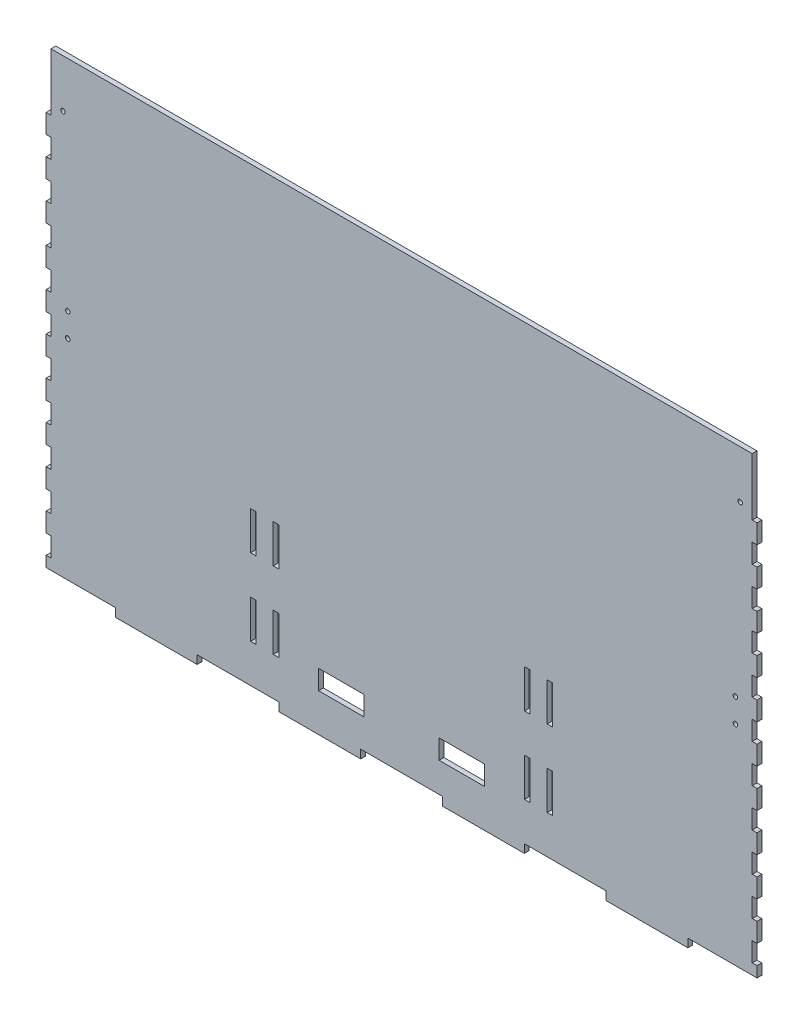
SolidWorks part; units mm, degrees
ref_plane "Front Plane" through (0, 0, 0) normal (0, 0, 1) x (1, 0, 0)
ref_plane "Top Plane" through (0, 0, 0) normal (0, 1, 0) x (1, 0, 0)
ref_plane "Right Plane" through (0, 0, 0) normal (1, 0, 0) x (0, 0, -1)
sketch "Sketch1" plane through (0, 0, 0) normal (0, 0, 1) x (1, 0, 0)
  line L0 (0, 139.7) -> (0, -139.7) construction
  line L1 (-406.4, 139.7) -> (406.4, 139.7)
  line L2 (-406.4, 139.7) -> (-406.4, -139.7)
  line L3 (-406.4, -139.7) -> (406.4, -139.7)
  line L4 (406.4, 139.7) -> (406.4, -139.7)
  line L49 (-381, 127) -> (-381, 114.3)
  line L54 (-381, 139.7) -> (-377.825, 139.7)
  line L55 (-381, 139.7) -> (-381, 127)
  line L56 (-381, 127) -> (-377.825, 127)
  line L57 (-377.825, 139.7) -> (-377.825, 127)
  line L58 (-381, 127) -> (-377.825, 127)
  line L59 (-377.825, 127) -> (-377.825, 114.3)
  line L60 (-381, 114.3) -> (-377.825, 114.3)
  line L61 (-381, 114.3) -> (-381, 101.6)
  line L62 (-381, 114.3) -> (-377.825, 114.3)
  line L63 (-377.825, 114.3) -> (-377.825, 101.6)
  line L64 (-381, 101.6) -> (-377.825, 101.6)
  line L65 (-381, 101.6) -> (-381, 88.9)
  line L66 (-381, 101.6) -> (-377.825, 101.6)
  line L67 (-377.825, 101.6) -> (-377.825, 88.9)
  line L68 (-381, 88.9) -> (-377.825, 88.9)
  line L69 (-381, 88.9) -> (-381, 76.2)
  line L70 (-381, 88.9) -> (-377.825, 88.9)
  line L71 (-377.825, 88.9) -> (-377.825, 76.2)
  line L72 (-381, 76.2) -> (-377.825, 76.2)
  line L73 (-381, 76.2) -> (-381, 63.5)
  line L74 (-381, 76.2) -> (-377.825, 76.2)
  line L75 (-377.825, 76.2) -> (-377.825, 63.5)
  line L76 (-381, 63.5) -> (-377.825, 63.5)
  line L77 (-381, 63.5) -> (-381, 50.8)
  line L78 (-381, 63.5) -> (-377.825, 63.5)
  line L79 (-377.825, 63.5) -> (-377.825, 50.8)
  line L80 (-381, 50.8) -> (-377.825, 50.8)
  line L81 (-381, 50.8) -> (-381, 38.1)
  line L82 (-381, 50.8) -> (-377.825, 50.8)
  line L83 (-377.825, 50.8) -> (-377.825, 38.1)
  line L84 (-381, 38.1) -> (-377.825, 38.1)
  line L85 (-381, 38.1) -> (-381, 25.4)
  line L86 (-381, 38.1) -> (-377.825, 38.1)
  line L87 (-377.825, 38.1) -> (-377.825, 25.4)
  line L88 (-381, 25.4) -> (-377.825, 25.4)
  line L89 (377.825, 127) -> (377.825, 114.3)
  line L90 (377.825, 139.7) -> (381, 139.7)
  line L91 (377.825, 139.7) -> (377.825, 127)
  line L92 (377.825, 127) -> (381, 127)
  line L93 (381, 139.7) -> (381, 127)
  line L94 (377.825, 127) -> (381, 127)
  line L95 (381, 127) -> (381, 114.3)
  line L96 (377.825, 114.3) -> (381, 114.3)
  line L97 (377.825, 114.3) -> (377.825, 101.6)
  line L98 (377.825, 114.3) -> (381, 114.3)
  line L99 (381, 114.3) -> (381, 101.6)
  line L100 (377.825, 101.6) -> (381, 101.6)
  line L101 (377.825, 101.6) -> (377.825, 88.9)
  line L102 (377.825, 101.6) -> (381, 101.6)
  line L103 (381, 101.6) -> (381, 88.9)
  line L104 (377.825, 88.9) -> (381, 88.9)
  line L105 (377.825, 88.9) -> (377.825, 76.2)
  line L106 (377.825, 88.9) -> (381, 88.9)
  line L107 (381, 88.9) -> (381, 76.2)
  line L108 (377.825, 76.2) -> (381, 76.2)
  line L109 (377.825, 76.2) -> (377.825, 63.5)
  line L110 (377.825, 76.2) -> (381, 76.2)
  line L111 (381, 76.2) -> (381, 63.5)
  line L112 (377.825, 63.5) -> (381, 63.5)
  line L113 (377.825, 63.5) -> (377.825, 50.8)
  line L114 (377.825, 63.5) -> (381, 63.5)
  line L115 (381, 63.5) -> (381, 50.8)
  line L116 (377.825, 50.8) -> (381, 50.8)
  line L117 (377.825, 50.8) -> (377.825, 38.1)
  line L118 (377.825, 50.8) -> (381, 50.8)
  line L119 (381, 50.8) -> (381, 38.1)
  line L120 (377.825, 38.1) -> (381, 38.1)
  line L121 (377.825, 38.1) -> (377.825, 25.4)
  line L122 (377.825, 38.1) -> (381, 38.1)
  line L123 (381, 38.1) -> (381, 25.4)
  line L124 (377.825, 25.4) -> (381, 25.4)
  line L125 (-352.2133, -134.112) -> (-352.2133, -139.7)
  line L126 (-406.4, -134.112) -> (-352.2133, -134.112)
  line L127 (-406.4, -134.112) -> (-406.4, -139.7)
  line L128 (-406.4, -139.7) -> (-352.2133, -139.7)
  line L129 (-352.2133, -134.112) -> (-352.2133, -139.7)
  line L130 (-352.2133, -134.112) -> (-298.0267, -134.112)
  line L131 (-298.0267, -134.112) -> (-298.0267, -139.7)
  line L132 (-352.2133, -139.7) -> (-298.0267, -139.7)
  line L133 (-298.0267, -134.112) -> (-298.0267, -139.7)
  line L134 (-298.0267, -134.112) -> (-243.84, -134.112)
  line L135 (-243.84, -134.112) -> (-243.84, -139.7)
  line L136 (-298.0267, -139.7) -> (-243.84, -139.7)
  line L137 (-243.84, -134.112) -> (-243.84, -139.7)
  line L138 (-243.84, -134.112) -> (-189.6533, -134.112)
  line L139 (-189.6533, -134.112) -> (-189.6533, -139.7)
  line L140 (-243.84, -139.7) -> (-189.6533, -139.7)
  line L141 (-189.6533, -134.112) -> (-189.6533, -139.7)
  line L142 (-189.6533, -134.112) -> (-135.4667, -134.112)
  line L143 (-135.4667, -134.112) -> (-135.4667, -139.7)
  line L144 (-189.6533, -139.7) -> (-135.4667, -139.7)
  line L145 (-135.4667, -134.112) -> (-135.4667, -139.7)
  line L146 (-135.4667, -134.112) -> (-81.28, -134.112)
  line L147 (-81.28, -134.112) -> (-81.28, -139.7)
  line L148 (-135.4667, -139.7) -> (-81.28, -139.7)
  line L149 (-81.28, -134.112) -> (-81.28, -139.7)
  line L150 (-81.28, -134.112) -> (-27.0933, -134.112)
  line L151 (-27.0933, -134.112) -> (-27.0933, -139.7)
  line L152 (-81.28, -139.7) -> (-27.0933, -139.7)
  line L153 (-27.0933, -134.112) -> (-27.0933, -139.7)
  line L154 (-27.0933, -134.112) -> (27.0933, -134.112)
  line L155 (27.0933, -134.112) -> (27.0933, -139.7)
  line L156 (-27.0933, -139.7) -> (27.0933, -139.7)
  line L157 (27.0933, -134.112) -> (27.0933, -139.7)
  line L158 (27.0933, -134.112) -> (81.28, -134.112)
  line L159 (81.28, -134.112) -> (81.28, -139.7)
  line L160 (27.0933, -139.7) -> (81.28, -139.7)
  line L161 (81.28, -134.112) -> (81.28, -139.7)
  line L162 (81.28, -134.112) -> (135.4667, -134.112)
  line L163 (135.4667, -134.112) -> (135.4667, -139.7)
  line L164 (81.28, -139.7) -> (135.4667, -139.7)
  line L165 (135.4667, -134.112) -> (135.4667, -139.7)
  line L166 (135.4667, -134.112) -> (189.6533, -134.112)
  line L167 (189.6533, -134.112) -> (189.6533, -139.7)
  line L168 (135.4667, -139.7) -> (189.6533, -139.7)
  line L169 (189.6533, -134.112) -> (189.6533, -139.7)
  line L170 (189.6533, -134.112) -> (243.84, -134.112)
  line L171 (243.84, -134.112) -> (243.84, -139.7)
  line L172 (189.6533, -139.7) -> (243.84, -139.7)
  line L173 (243.84, -134.112) -> (243.84, -139.7)
  line L174 (243.84, -134.112) -> (298.0267, -134.112)
  line L175 (298.0267, -134.112) -> (298.0267, -139.7)
  line L176 (243.84, -139.7) -> (298.0267, -139.7)
  line L177 (298.0267, -134.112) -> (298.0267, -139.7)
  line L178 (298.0267, -134.112) -> (352.2133, -134.112)
  line L179 (352.2133, -134.112) -> (352.2133, -139.7)
  line L180 (298.0267, -139.7) -> (352.2133, -139.7)
  line L181 (352.2133, -134.112) -> (352.2133, -139.7)
  line L182 (352.2133, -134.112) -> (406.4, -134.112)
  line L183 (406.4, -134.112) -> (406.4, -139.7)
  line L184 (352.2133, -139.7) -> (406.4, -139.7)
  line L205 (-90.678, 84.5227) -> (-90.678, -139.7) construction
  line L206 (90.678, 84.5227) -> (90.678, -139.7) construction
  line L207 (-90.678, -27.5886) -> (90.678, -27.5886) construction
  line L208 (-381, 25.4) -> (-381, 12.7)
  line L209 (-381, 25.4) -> (-377.825, 25.4)
  line L210 (-377.825, 25.4) -> (-377.825, 12.7)
  line L211 (-381, 12.7) -> (-377.825, 12.7)
  line L212 (-381, 12.7) -> (-381, 0)
  line L213 (-381, 12.7) -> (-377.825, 12.7)
  line L214 (-377.825, 12.7) -> (-377.825, 0)
  line L215 (-381, 0) -> (-377.825, 0)
  line L224 (-377.825, 0) -> (377.825, 0) construction
  line L229 (377.825, 25.4) -> (377.825, 12.7)
  line L230 (377.825, 25.4) -> (381, 25.4)
  line L231 (381, 25.4) -> (381, 12.7)
  line L232 (377.825, 12.7) -> (381, 12.7)
  line L233 (377.825, 12.7) -> (377.825, 0)
  line L234 (377.825, 12.7) -> (381, 12.7)
  line L235 (381, 12.7) -> (381, 0)
  line L236 (377.825, 0) -> (381, 0)
  line L237 (-381, 0) -> (-381, -12.7)
  line L238 (-381, 0) -> (-377.825, 0)
  line L239 (-377.825, 0) -> (-377.825, -12.7)
  line L240 (-381, -12.7) -> (-377.825, -12.7)
  line L241 (-381, -12.7) -> (-381, -25.4)
  line L242 (-381, -12.7) -> (-377.825, -12.7)
  line L243 (-377.825, -12.7) -> (-377.825, -25.4)
  line L244 (-381, -25.4) -> (-377.825, -25.4)
  line L245 (-381, -25.4) -> (-381, -38.1)
  line L246 (-381, -25.4) -> (-377.825, -25.4)
  line L247 (-377.825, -25.4) -> (-377.825, -38.1)
  line L248 (-381, -38.1) -> (-377.825, -38.1)
  line L249 (-381, -38.1) -> (-381, -50.8)
  line L250 (-381, -38.1) -> (-377.825, -38.1)
  line L251 (-377.825, -38.1) -> (-377.825, -50.8)
  line L252 (-381, -50.8) -> (-377.825, -50.8)
  line L253 (-381, -50.8) -> (-381, -63.5)
  line L254 (-381, -50.8) -> (-377.825, -50.8)
  line L255 (-377.825, -50.8) -> (-377.825, -63.5)
  line L256 (-381, -63.5) -> (-377.825, -63.5)
  line L257 (-381, -63.5) -> (-381, -76.2)
  line L258 (-381, -63.5) -> (-377.825, -63.5)
  line L259 (-377.825, -63.5) -> (-377.825, -76.2)
  line L260 (-381, -76.2) -> (-377.825, -76.2)
  line L261 (-381, -76.2) -> (-381, -88.9)
  line L262 (-381, -76.2) -> (-377.825, -76.2)
  line L263 (-377.825, -76.2) -> (-377.825, -88.9)
  line L264 (-381, -88.9) -> (-377.825, -88.9)
  line L265 (-381, -88.9) -> (-381, -101.6)
  line L266 (-381, -88.9) -> (-377.825, -88.9)
  line L267 (-377.825, -88.9) -> (-377.825, -101.6)
  line L268 (-381, -101.6) -> (-377.825, -101.6)
  line L269 (-381, -101.6) -> (-381, -114.3)
  line L270 (-381, -101.6) -> (-377.825, -101.6)
  line L271 (-377.825, -101.6) -> (-377.825, -114.3)
  line L272 (-381, -114.3) -> (-377.825, -114.3)
  line L273 (-381, -114.3) -> (-381, -127)
  line L274 (-381, -114.3) -> (-377.825, -114.3)
  line L275 (-377.825, -114.3) -> (-377.825, -127)
  line L276 (-381, -127) -> (-377.825, -127)
  line L277 (-381, -127) -> (-381, -139.7)
  line L278 (-381, -127) -> (-377.825, -127)
  line L279 (-377.825, -127) -> (-377.825, -139.7)
  line L280 (-381, -139.7) -> (-377.825, -139.7)
  line L281 (377.825, 0) -> (377.825, -12.7)
  line L282 (377.825, 0) -> (381, 0)
  line L283 (381, 0) -> (381, -12.7)
  line L284 (377.825, -12.7) -> (381, -12.7)
  line L285 (377.825, -12.7) -> (377.825, -25.4)
  line L286 (377.825, -12.7) -> (381, -12.7)
  line L287 (381, -12.7) -> (381, -25.4)
  line L288 (377.825, -25.4) -> (381, -25.4)
  line L289 (377.825, -25.4) -> (377.825, -38.1)
  line L290 (377.825, -25.4) -> (381, -25.4)
  line L291 (381, -25.4) -> (381, -38.1)
  line L292 (377.825, -38.1) -> (381, -38.1)
  line L293 (377.825, -38.1) -> (377.825, -50.8)
  line L294 (377.825, -38.1) -> (381, -38.1)
  line L295 (381, -38.1) -> (381, -50.8)
  line L296 (377.825, -50.8) -> (381, -50.8)
  line L297 (377.825, -50.8) -> (377.825, -63.5)
  line L298 (377.825, -50.8) -> (381, -50.8)
  line L299 (381, -50.8) -> (381, -63.5)
  line L300 (377.825, -63.5) -> (381, -63.5)
  line L301 (377.825, -63.5) -> (377.825, -76.2)
  line L302 (377.825, -63.5) -> (381, -63.5)
  line L303 (381, -63.5) -> (381, -76.2)
  line L304 (377.825, -76.2) -> (381, -76.2)
  line L305 (377.825, -76.2) -> (377.825, -88.9)
  line L306 (377.825, -76.2) -> (381, -76.2)
  line L307 (381, -76.2) -> (381, -88.9)
  line L308 (377.825, -88.9) -> (381, -88.9)
  line L309 (377.825, -88.9) -> (377.825, -101.6)
  line L310 (377.825, -88.9) -> (381, -88.9)
  line L311 (381, -88.9) -> (381, -101.6)
  line L312 (377.825, -101.6) -> (381, -101.6)
  line L313 (377.825, -101.6) -> (377.825, -114.3)
  line L314 (377.825, -101.6) -> (381, -101.6)
  line L315 (381, -101.6) -> (381, -114.3)
  line L316 (377.825, -114.3) -> (381, -114.3)
  line L317 (377.825, -114.3) -> (377.825, -127)
  line L318 (377.825, -114.3) -> (381, -114.3)
  line L319 (381, -114.3) -> (381, -127)
  line L320 (377.825, -127) -> (381, -127)
  line L321 (377.825, -127) -> (377.825, -139.7)
  line L322 (377.825, -127) -> (381, -127)
  line L323 (381, -127) -> (381, -139.7)
  line L324 (377.825, -139.7) -> (381, -139.7)
  point P6 (0, 0)
  point P128 (0, -27.5886)
  point P153 (0, 0)
  dimension "D4" = 12.7
  dimension "D5" = 3.175
  dimension "D10" = 181.356
  dimension "D12" = 755.65
  dimension "D8" = 812.8
  dimension "D11" = 54.1867
  dimension "D2" = 273.812
  dimension "D9" = 279.4
  dimension "D3" = 22
  dimension "D7" = 15
  dimension "D6" = 22
extrude "Main Extrude" add sketch "Sketch1" along normal blind 3.175 contours L321 L317 L313 L309 L305 L301 L297 L293 L289 L285 L281 L233 L229 L121 L117 L113 L109 L105 L101 L97 L89 L91 L1 L57 L59 L63 L67 L71 L75 L79 L83 L87 L210 L214 L239 L243 L247 L251 L255 L259 L263 L267 L271 L275 L279 L126 L130 L134 L138 L142 L146 | L277 L273 L269 L265 L261 L257 L253 L249 L245 L241 L237 L212 L208 L85 L81 L77 L73 L69 L65 L61 L49 L55 L1 L2 L126 | L319 L323 L182 L4 L1 L93 L95 L99 L103 L107 L111 L115 L119 L123 L231 L235 L283 L287 L291 L295 L299 L303 L307 L311 L315 | L126 L279 L3 L125 | L135 L134 L131 L3 | L143 L142 L139 L3 | L151 L150 L147 L3 | L159 L158 L155 L3 | L167 L166 L163 L3 | L175 L174 L171 L3 | L323 L182 L321 L184 | L89 L96 L95 L92 | L101 L104 L103 L100 | L109 L112 L111 L108 | L117 L120 L119 L116 | L229 L232 L231 L124 | L281 L284 L283 L236 | L289 L292 L291 L288 | L297 L300 L299 L296 | L305 L308 L307 L304 | L313 L316 L315 L312 | L323 L320 L321 L182 | L49 L60 L59 L56 | L65 L68 L67 L64 | L73 L76 L75 L72 | L81 L84 L83 L80 | L208 L211 L210 L88 | L237 L240 L239 L215 | L245 L248 L247 L244 | L253 L256 L255 L252 | L261 L264 L263 L260 | L269 L272 L271 L268 | L279 L276 L277 L126 | L277 L126 L2 L3 | L321 L182 L179 L3 | L182 L323 L3 L4 | L279 L126 L277 L128 region at (-393.7, 2.794, 0) region at (-393.7, -136.906, 0) region at (0, 2.794, 0) region at (-379.4125, 120.65, 0) region at (-379.4125, -130.556, 0) region at (-379.4125, -136.906, 0) region at (-365.0192, -136.906, 0) region at (393.7, 2.794, 0) region at (379.4125, 120.65, 0) region at (-379.4125, 95.25, 0) region at (-379.4125, -107.95, 0) region at (-270.9333, -136.906, 0) region at (393.7, -136.906, 0) region at (379.4125, 95.25, 0) region at (-379.4125, 69.85, 0) region at (-379.4125, -82.55, 0) region at (379.4125, -136.906, 0) region at (379.4125, -130.556, 0) region at (-162.56, -136.906, 0) region at (365.0192, -136.906, 0) region at (379.4125, 69.85, 0) region at (-379.4125, 44.45, 0) region at (-379.4125, -57.15, 0) region at (379.4125, -107.95, 0) region at (-54.1867, -136.906, 0) region at (270.9333, -136.906, 0) region at (379.4125, 44.45, 0) region at (-379.4125, 19.05, 0) region at (-379.4125, -31.75, 0) region at (379.4125, -82.55, 0) region at (54.1867, -136.906, 0) region at (162.56, -136.906, 0) region at (379.4125, 19.05, 0) region at (-379.4125, -6.35, 0) region at (379.4125, -57.15, 0) region at (379.4125, -6.35, 0) region at (379.4125, -31.75, 0)
sketch "Sketch8" plane through (0, 0, 3.175) normal (0, 0, 1) x (1, 0, 0)
  line L0 (-406.4, 139.7) -> (-406.4, -139.7) construction
  line L1 (-381, 28.2575) -> (-384.175, 28.2575)
  line L2 (-381, 28.2575) -> (-381, -3.6195)
  line L3 (-381, -3.6195) -> (-384.175, -3.6195)
  line L4 (-384.175, 28.2575) -> (-384.175, -3.6195)
  line L5 (-406.4, -139.7) -> (-352.2133, -139.7) construction
  line L6 (381, 28.2575) -> (384.175, 28.2575)
  line L7 (381, 28.2575) -> (381, -3.6195)
  line L8 (381, -3.6195) -> (384.175, -3.6195)
  line L9 (384.175, 28.2575) -> (384.175, -3.6195)
  line L11 (-381, 88.9) -> (-381, 76.2) construction
  line L12 (-352.2133, -134.112) -> (-298.0267, -134.112) construction
  line L13 (381, 88.9) -> (381, 76.2) construction
  line L14 (-393.7, -120.65) -> (393.7, -120.65) construction
  circle A0 centre (-393.7, -120.65) radius 1.5
  circle A1 centre (393.7, -120.65) radius 1.5
  point P6 (0, -120.65)
  point P16 (-384.175, 12.319)
  dimension "D5" = 3
  dimension "D1" = 31.877
  dimension "D2" = 3.175
  dimension "D3" = 146.431
  dimension "D4" = 19.05
  dimension "D6" = 12.7
extrude "Mount Holes" cut sketch "Sketch8" against normal through all
sketch "Sketch3" plane through (0, 0, 3.175) normal (0, 0, 1) x (1, 0, 0)
  line L0 (-135.4667, -134.112) -> (-81.28, -134.112) construction
  line L1 (-96.52, 126.492) -> (-84.836, 126.492)
  line L2 (-96.52, 126.492) -> (-96.52, -134.112)
  line L3 (-96.52, -134.112) -> (-84.836, -134.112)
  line L4 (-84.836, 126.492) -> (-84.836, -134.112)
  line L5 (81.28, -134.112) -> (135.4667, -134.112) construction
  line L6 (84.836, 126.492) -> (96.52, 126.492)
  line L7 (84.836, 126.492) -> (84.836, -134.112)
  line L8 (84.836, -134.112) -> (96.52, -134.112)
  line L9 (96.52, 126.492) -> (96.52, -134.112)
  line L10 (-84.836, -3.81) -> (84.836, -3.81) construction
  line L12 (-106.553, 10.3505) -> (-74.803, 10.3505)
  line L13 (-106.553, 10.3505) -> (-106.553, 0.8255)
  line L14 (-106.553, 0.8255) -> (-74.803, 0.8255)
  line L15 (-74.803, 10.3505) -> (-74.803, 0.8255)
  line L16 (74.803, 10.3505) -> (106.553, 10.3505)
  line L17 (74.803, 10.3505) -> (74.803, 0.8255)
  line L18 (74.803, 0.8255) -> (106.553, 0.8255)
  line L19 (106.553, 10.3505) -> (106.553, 0.8255)
  line L20 (-96.52, 126.492) -> (-92.6465, 126.492)
  line L21 (-96.52, 126.492) -> (-96.52, 82.042)
  line L22 (-96.52, 82.042) -> (-92.6465, 82.042)
  line L23 (-92.6465, 126.492) -> (-92.6465, 82.042)
  line L24 (-84.836, 126.492) -> (-88.7095, 126.492)
  line L25 (-84.836, 126.492) -> (-84.836, 82.042)
  line L26 (-84.836, 82.042) -> (-88.7095, 82.042)
  line L27 (-88.7095, 126.492) -> (-88.7095, 82.042)
  line L28 (84.836, 126.492) -> (88.7095, 126.492)
  line L29 (84.836, 126.492) -> (84.836, 82.042)
  line L30 (84.836, 82.042) -> (88.7095, 82.042)
  line L31 (88.7095, 126.492) -> (88.7095, 82.042)
  line L32 (96.52, 126.492) -> (92.6465, 126.492)
  line L33 (96.52, 126.492) -> (96.52, 82.042)
  line L34 (96.52, 82.042) -> (92.6465, 82.042)
  line L35 (92.6465, 126.492) -> (92.6465, 82.042)
  point P14 (-90.678, 126.492)
  point P15 (90.678, 126.492)
  point P16 (0, -3.81)
  point P27 (-90.678, 10.3505)
  point P28 (90.678, 10.3505)
  point P29 (-74.803, 5.588)
  dimension "D1" = 11.684
  dimension "D2" = 260.604
  dimension "D3" = 181.356
  dimension "D4" = 9.525
  dimension "D5" = 139.7
  dimension "D6" = 31.75
  dimension "D8" = 3.937
  dimension "D7" = 44.45
extrude "Door Slots" [suppressed] cut sketch "Sketch3" against normal through all contours L2 L12 L4 L1 | L2 L14 L4 L12 | L15 L12 L4 L14 | L13 L14 L2 L12 | L14 L2 L3 L4 | L7 L16 L9 L6 | L7 L18 L9 L16 | L19 L16 L9 L18 | L17 L18 L7 L16 | L18 L7 L8 L9
sketch "Sketch4" plane through (0, 0, 0) normal (0, 0, 1) x (1, 0, 0)
  line L1 (-81.28, -139.7) -> (-27.0933, -139.7) construction
  line L2 (-55.88, -112.41) -> (-52.578, -112.41)
  line L3 (-52.578, -112.41) -> (-52.578, -106.172)
  line L4 (-52.578, -106.172) -> (-1.778, -106.172)
  line L5 (-1.778, -106.172) -> (-1.778, -112.41)
  line L6 (-1.778, -112.41) -> (1.524, -112.41)
  line L9 (-55.88, -112.41) -> (-55.88, -134.112)
  line L10 (-55.88, -134.112) -> (-52.578, -134.112)
  line L11 (-52.578, -134.112) -> (-52.578, -139.7)
  line L12 (1.524, -112.41) -> (1.524, -134.112)
  line L13 (1.524, -134.112) -> (-1.778, -134.112)
  line L14 (-1.778, -134.112) -> (-1.778, -139.7)
  line L15 (-52.578, -139.7) -> (-1.778, -139.7)
  line L16 (-27.0933, -134.112) -> (27.0933, -134.112) construction
  line L17 (-27.0933, -134.112) -> (27.0933, -134.112) construction
  line L18 (12.128, -101.642) -> (42.228, -101.642)
  line L19 (12.128, -101.642) -> (12.128, -114.492)
  line L20 (12.128, -114.492) -> (42.228, -114.492)
  line L21 (42.228, -101.642) -> (42.228, -114.492)
  line L24 (-96.52, -134.112) -> (-84.836, -134.112) construction
  line L25 (84.836, -134.112) -> (96.52, -134.112) construction
  point P9 (-27.178, -106.172)
  point P10 (-27.178, -139.7)
  point P22 (27.178, -114.492)
  point P25 (90.678, -134.112)
  point P26 (12.128, -108.067)
  point P30 (-90.678, -134.112)
  dimension "D1" = 50.8
  dimension "D2" = 3.302
  dimension "D4" = 21.702
  dimension "D5" = 30.1
  dimension "D6" = 12.85
  dimension "D9" = 63.5
  dimension "D8" = 63.5
  dimension "D3" = 27.94
  dimension "D7" = 26.045
extrude "Trough and Lever Holes" [suppressed] cut sketch "Sketch4" along normal through all contours L11 L15 L14 L13 L12 L6 L5 L4 L3 L2 L9 L10 | L21 L18 L19 L20
sketch "Sketch5" plane through (0, 0, 3.175) normal (0, 0, 1) x (1, 0, 0)
  line L0 (-90.678, 126.492) -> (-90.678, -134.112) construction
  line L1 (-96.52, 126.492) -> (-84.836, 126.492) construction
  line L2 (-96.52, -134.112) -> (-84.836, -134.112) construction
  line L3 (90.678, 126.492) -> (90.678, -134.112) construction
  line L4 (84.836, 126.492) -> (96.52, 126.492) construction
  line L5 (84.836, -134.112) -> (96.52, -134.112) construction
  line L6 (-135.4667, -134.112) -> (-81.28, -134.112) construction
  line L19 (-99.998, -134.112) -> (-96.3199, -134.112)
  line L20 (-99.998, -134.112) -> (-99.998, -108.712)
  line L21 (-99.998, -108.712) -> (-96.3199, -108.712)
  line L22 (-96.3199, -134.112) -> (-96.3199, -108.712)
  line L24 (-99.998, -108.712) -> (-96.3199, -108.712)
  line L25 (-99.998, -108.712) -> (-99.998, -83.312)
  line L26 (-99.998, -83.312) -> (-96.3199, -83.312)
  line L27 (-96.3199, -108.712) -> (-96.3199, -83.312)
  line L28 (-96.3199, -83.312) -> (-99.998, -83.312)
  line L29 (-96.3199, -83.312) -> (-96.3199, -57.912)
  line L30 (-96.3199, -57.912) -> (-99.998, -57.912)
  line L31 (-99.998, -83.312) -> (-99.998, -57.912)
  line L32 (-99.998, -57.912) -> (-96.3199, -57.912)
  line L33 (-99.998, -57.912) -> (-99.998, -32.512)
  line L34 (-99.998, -32.512) -> (-96.3199, -32.512)
  line L35 (-96.3199, -57.912) -> (-96.3199, -32.512)
  line L36 (-96.3199, -32.512) -> (-99.998, -32.512)
  line L37 (-96.3199, -32.512) -> (-96.3199, -7.112)
  line L38 (-96.3199, -7.112) -> (-99.998, -7.112)
  line L39 (-99.998, -32.512) -> (-99.998, -7.112)
  line L40 (-81.358, -108.712) -> (-85.0361, -108.712)
  line L41 (-85.0361, -134.112) -> (-85.0361, -108.712)
  line L42 (-81.358, -134.112) -> (-85.0361, -134.112)
  line L43 (-81.358, -134.112) -> (-81.358, -108.712)
  line L44 (-81.358, -83.312) -> (-85.0361, -83.312)
  line L45 (-85.0361, -108.712) -> (-85.0361, -83.312)
  line L46 (-81.358, -108.712) -> (-85.0361, -108.712)
  line L47 (-81.358, -108.712) -> (-81.358, -83.312)
  line L48 (-85.0361, -57.912) -> (-81.358, -57.912)
  line L49 (-81.358, -83.312) -> (-81.358, -57.912)
  line L50 (-85.0361, -83.312) -> (-81.358, -83.312)
  line L51 (-85.0361, -83.312) -> (-85.0361, -57.912)
  line L52 (-81.358, -32.512) -> (-85.0361, -32.512)
  line L53 (-85.0361, -57.912) -> (-85.0361, -32.512)
  line L54 (-81.358, -57.912) -> (-85.0361, -57.912)
  line L55 (-81.358, -57.912) -> (-81.358, -32.512)
  line L56 (-85.0361, -7.112) -> (-81.358, -7.112)
  line L57 (-81.358, -32.512) -> (-81.358, -7.112)
  line L58 (-85.0361, -32.512) -> (-81.358, -32.512)
  line L59 (-85.0361, -32.512) -> (-85.0361, -7.112)
  line L60 (0, -1.7463) -> (0, 1.7463) construction
  line L61 (99.998, -108.712) -> (96.3199, -108.712)
  line L62 (96.3199, -134.112) -> (96.3199, -108.712)
  line L63 (99.998, -134.112) -> (96.3199, -134.112)
  line L64 (99.998, -134.112) -> (99.998, -108.712)
  line L65 (99.998, -83.312) -> (96.3199, -83.312)
  line L66 (96.3199, -108.712) -> (96.3199, -83.312)
  line L67 (99.998, -108.712) -> (96.3199, -108.712)
  line L68 (99.998, -108.712) -> (99.998, -83.312)
  line L69 (96.3199, -57.912) -> (99.998, -57.912)
  line L70 (99.998, -83.312) -> (99.998, -57.912)
  line L71 (96.3199, -83.312) -> (99.998, -83.312)
  line L72 (96.3199, -83.312) -> (96.3199, -57.912)
  line L73 (99.998, -32.512) -> (96.3199, -32.512)
  line L74 (96.3199, -57.912) -> (96.3199, -32.512)
  line L75 (99.998, -57.912) -> (96.3199, -57.912)
  line L76 (99.998, -57.912) -> (99.998, -32.512)
  line L77 (96.3199, -7.112) -> (99.998, -7.112)
  line L78 (99.998, -32.512) -> (99.998, -7.112)
  line L79 (96.3199, -32.512) -> (99.998, -32.512)
  line L80 (96.3199, -32.512) -> (96.3199, -7.112)
  line L81 (85.0361, -32.512) -> (85.0361, -7.112)
  line L82 (85.0361, -32.512) -> (81.358, -32.512)
  line L83 (81.358, -32.512) -> (81.358, -7.112)
  line L84 (85.0361, -7.112) -> (81.358, -7.112)
  line L85 (81.358, -57.912) -> (81.358, -32.512)
  line L86 (81.358, -57.912) -> (85.0361, -57.912)
  line L87 (85.0361, -57.912) -> (85.0361, -32.512)
  line L88 (81.358, -32.512) -> (85.0361, -32.512)
  line L89 (85.0361, -83.312) -> (85.0361, -57.912)
  line L90 (85.0361, -83.312) -> (81.358, -83.312)
  line L91 (81.358, -83.312) -> (81.358, -57.912)
  line L92 (85.0361, -57.912) -> (81.358, -57.912)
  line L93 (81.358, -108.712) -> (81.358, -83.312)
  line L94 (81.358, -108.712) -> (85.0361, -108.712)
  line L95 (85.0361, -108.712) -> (85.0361, -83.312)
  line L96 (81.358, -83.312) -> (85.0361, -83.312)
  line L97 (81.358, -134.112) -> (81.358, -108.712)
  line L98 (81.358, -134.112) -> (85.0361, -134.112)
  line L99 (85.0361, -134.112) -> (85.0361, -108.712)
  line L100 (81.358, -108.712) -> (85.0361, -108.712)
  dimension "D1" = 25.4
  dimension "D3" = 5.6419
  dimension "D2" = 9.32
extrude "Door Guide Slots" cut sketch "Sketch5" against normal through all contours L21 L27 L26 L25 | L30 L35 L34 L33 | L48 L55 L52 L53 | L40 L47 L44 L45 | L86 L87 L82 L85 | L94 L95 L90 L93 | L69 L76 L73 L74 | L61 L68 L65 L66 region at (-98.1589, -96.012, 3.175) region at (-98.1589, -45.212, 3.175) region at (-83.1971, -96.012, 3.175) region at (-83.1971, -45.212, 3.175) region at (98.1589, -96.012, 3.175) region at (98.1589, -45.212, 3.175) region at (83.1971, -45.212, 3.175) region at (83.1971, -96.012, 3.175)
sketch "Sketch7" plane through (0, 0, 3.175) normal (0, 0, 1) x (1, 0, 0)
  line L0 (-24.828, -108.067) -> (24.828, -108.067) construction
  line L1 (-54.928, -101.642) -> (-24.828, -101.642)
  line L2 (-54.928, -101.642) -> (-54.928, -114.492)
  line L3 (-54.928, -114.492) -> (-24.828, -114.492)
  line L4 (-24.828, -101.642) -> (-24.828, -114.492)
  line L5 (54.928, -101.642) -> (24.828, -101.642)
  line L6 (54.928, -101.642) -> (54.928, -114.492)
  line L7 (54.928, -114.492) -> (24.828, -114.492)
  line L8 (24.828, -101.642) -> (24.828, -114.492)
  line L9 (0, -108.067) -> (0, 0) construction
  line L10 (-96.52, -134.112) -> (-84.836, -134.112) construction
  line L12 (-135.4667, -134.112) -> (-81.28, -134.112) construction
  point P12 (-54.928, -108.067)
  point P15 (-39.878, -101.642)
  point P18 (-90.678, -134.112)
  dimension "D1" = 12.85
  dimension "D2" = 30.1
  dimension "D3" = 50.8
  dimension "D4" = 26.045
extrude "Lever Holes" cut sketch "Sketch7" against normal through all
sketch "Sketch10" [suppressed] plane through (0, 0, 3.175) normal (0, 0, 1) x (1, 0, 0)
  line L0 (-101.678, 127.492) -> (-79.678, 127.492) construction
  line L2 (-92.6465, 126.492) -> (-88.7095, 126.492) construction
  line L3 (-90.678, 127.492) -> (-90.678, 126.492) construction
  line L4 (79.678, 127.492) -> (101.678, 127.492) construction
  line L5 (90.678, 127.492) -> (90.678, 126.492) construction
  line L6 (88.7095, 126.492) -> (92.6465, 126.492) construction
  circle A0 centre (-101.678, 127.492) radius 1.5
  circle A1 centre (-79.678, 127.492) radius 1.5
  circle A2 centre (79.678, 127.492) radius 1.5
  circle A3 centre (101.678, 127.492) radius 1.5
  dimension "D1" = 3
  dimension "D2" = 22
  dimension "D3" = 1
extrude "Door Guide Mount Holes" [suppressed] cut sketch "Sketch10" against normal through all
sketch "Sketch12" plane through (0, 0, 3.175) normal (0, 0, 1) x (1, 0, 0)
  line L0 (-246.507, 20.193) -> (-246.507, 4.445) construction
  line L1 (-221.107, 20.193) -> (-221.107, 4.445) construction
  line L2 (-246.507, 20.193) -> (-221.107, 20.193) construction
  line L3 (-246.507, 4.445) -> (-221.107, 4.445) construction
  line L4 (-243.332, 133.35) -> (-224.282, 133.35) construction
  line L5 (-406.4, 139.7) -> (406.4, 139.7) construction
  line L6 (-233.807, 20.193) -> (-233.807, 133.35) construction
  line L7 (-243.84, -134.112) -> (-189.6533, -134.112) construction
  line L8 (0, -1.7463) -> (0, 1.7463) construction
  line L9 (233.807, 20.193) -> (233.807, 133.35) construction
  line L10 (243.332, 133.35) -> (224.282, 133.35) construction
  line L11 (246.507, 4.445) -> (221.107, 4.445) construction
  line L12 (246.507, 20.193) -> (221.107, 20.193) construction
  line L13 (221.107, 20.193) -> (221.107, 4.445) construction
  line L14 (246.507, 20.193) -> (246.507, 4.445) construction
  circle A0 centre (-246.507, 20.193) radius 1.5
  circle A1 centre (-246.507, 4.445) radius 1.5
  circle A2 centre (-221.107, 4.445) radius 1.5
  circle A3 centre (-221.107, 20.193) radius 1.5
  circle A4 centre (-243.332, 133.35) radius 1.5
  circle A5 centre (-224.282, 133.35) radius 1.5
  circle A6 centre (224.282, 133.35) radius 1.5
  circle A7 centre (243.332, 133.35) radius 1.5
  circle A8 centre (221.107, 20.193) radius 1.5
  circle A9 centre (221.107, 4.445) radius 1.5
  circle A10 centre (246.507, 4.445) radius 1.5
  circle A11 centre (246.507, 20.193) radius 1.5
  point P12 (-233.807, 133.35)
  dimension "D1" = 3
  dimension "D2" = 233.807
  dimension "D3" = 19.05
  dimension "D4" = 6.35
  dimension "D5" = 25.4
  dimension "D6" = 15.748
  dimension "D7" = 138.557
extrude "Extension Clip Holes" cut sketch "Sketch12" against normal through all
sketch "Sketch11" plane through (0, 0, 3.175) normal (0, 0, 1) x (1, 0, 0)
  line L0 (-232.2195, 139.7) -> (-232.2195, 127)
  line L1 (-232.2195, 127) -> (-235.3945, 127)
  line L2 (-235.3945, 127) -> (-235.3945, 114.3)
  line L3 (-235.3945, 114.3) -> (-232.2195, 114.3)
  line L4 (232.2195, 139.7) -> (232.2195, 127)
  line L5 (232.2195, 127) -> (235.3945, 127)
  line L6 (235.3945, 127) -> (235.3945, 114.3)
  line L7 (235.3945, 114.3) -> (232.2195, 114.3)
  line L9 (-381, 127) -> (-377.825, 127) construction
  line L10 (-377.825, 139.7) -> (-377.825, 127) construction
  line L11 (235.3945, 120.65) -> (-235.3945, 120.65) construction
  line L12 (-232.2195, 114.3) -> (-232.2195, 101.6)
  line L13 (-232.2195, 101.6) -> (-235.3945, 101.6)
  line L14 (-235.3945, 101.6) -> (-235.3945, 88.9)
  line L15 (-235.3945, 88.9) -> (-232.2195, 88.9)
  line L16 (232.2195, 114.3) -> (232.2195, 101.6)
  line L17 (232.2195, 101.6) -> (235.3945, 101.6)
  line L18 (235.3945, 101.6) -> (235.3945, 88.9)
  line L19 (235.3945, 88.9) -> (232.2195, 88.9)
  line L20 (-232.2195, 88.9) -> (-232.2195, 76.2)
  line L21 (-232.2195, 76.2) -> (-235.3945, 76.2)
  line L22 (-235.3945, 76.2) -> (-235.3945, 63.5)
  line L23 (-235.3945, 63.5) -> (-232.2195, 63.5)
  line L24 (232.2195, 88.9) -> (232.2195, 76.2)
  line L25 (232.2195, 76.2) -> (235.3945, 76.2)
  line L26 (235.3945, 76.2) -> (235.3945, 63.5)
  line L27 (235.3945, 63.5) -> (232.2195, 63.5)
  line L28 (-232.2195, 63.5) -> (-232.2195, 50.8)
  line L29 (-232.2195, 50.8) -> (-235.3945, 50.8)
  line L30 (-235.3945, 50.8) -> (-235.3945, 38.1)
  line L31 (-235.3945, 38.1) -> (-232.2195, 38.1)
  line L32 (232.2195, 63.5) -> (232.2195, 50.8)
  line L33 (232.2195, 50.8) -> (235.3945, 50.8)
  line L34 (235.3945, 50.8) -> (235.3945, 38.1)
  line L35 (235.3945, 38.1) -> (232.2195, 38.1)
  line L36 (-232.2195, 38.1) -> (-232.2195, 25.4)
  line L37 (-232.2195, 25.4) -> (-235.3945, 25.4)
  line L38 (-235.3945, 25.4) -> (-235.3945, 12.7)
  line L39 (-235.3945, 12.7) -> (-232.2195, 12.7)
  line L40 (232.2195, 38.1) -> (232.2195, 25.4)
  line L41 (232.2195, 25.4) -> (235.3945, 25.4)
  line L42 (235.3945, 25.4) -> (235.3945, 12.7)
  line L43 (235.3945, 12.7) -> (232.2195, 12.7)
  line L44 (-232.2195, 12.7) -> (-232.2195, 0)
  line L45 (-232.2195, 0) -> (-235.3945, 0)
  line L46 (-235.3945, 0) -> (-235.3945, -12.7)
  line L47 (-235.3945, -12.7) -> (-232.2195, -12.7)
  line L48 (232.2195, 12.7) -> (232.2195, 0)
  line L50 (232.2195, 0) -> (235.3945, 0)
  line L52 (235.3945, 0) -> (235.3945, -12.7)
  line L53 (235.3945, -12.7) -> (232.2195, -12.7)
  line L54 (-232.2195, -12.7) -> (-232.2195, -25.4)
  line L55 (-232.2195, -25.4) -> (-235.3945, -25.4)
  line L56 (-235.3945, -25.4) -> (-235.3945, -38.1)
  line L57 (-235.3945, -38.1) -> (-232.2195, -38.1)
  line L58 (232.2195, -12.7) -> (232.2195, -25.4)
  line L59 (232.2195, -25.4) -> (235.3945, -25.4)
  line L60 (235.3945, -25.4) -> (235.3945, -38.1)
  line L61 (235.3945, -38.1) -> (232.2195, -38.1)
  line L62 (-232.2195, -38.1) -> (-232.2195, -50.8)
  line L63 (-232.2195, -50.8) -> (-235.3945, -50.8)
  line L64 (-235.3945, -50.8) -> (-235.3945, -63.5)
  line L65 (-235.3945, -63.5) -> (-232.2195, -63.5)
  line L66 (232.2195, -38.1) -> (232.2195, -50.8)
  line L67 (232.2195, -50.8) -> (235.3945, -50.8)
  line L68 (235.3945, -50.8) -> (235.3945, -63.5)
  line L69 (235.3945, -63.5) -> (232.2195, -63.5)
  line L70 (-232.2195, -63.5) -> (-232.2195, -76.2)
  line L71 (-232.2195, -76.2) -> (-235.3945, -76.2)
  line L72 (-235.3945, -76.2) -> (-235.3945, -88.9)
  line L73 (-235.3945, -88.9) -> (-232.2195, -88.9)
  line L74 (232.2195, -63.5) -> (232.2195, -76.2)
  line L75 (232.2195, -76.2) -> (235.3945, -76.2)
  line L76 (235.3945, -76.2) -> (235.3945, -88.9)
  line L77 (235.3945, -88.9) -> (232.2195, -88.9)
  line L78 (-232.2195, -88.9) -> (-232.2195, -101.6)
  line L79 (-232.2195, -101.6) -> (-235.3945, -101.6)
  line L80 (-235.3945, -101.6) -> (-235.3945, -114.3)
  line L81 (-235.3945, -114.3) -> (-232.2195, -114.3)
  line L82 (232.2195, -88.9) -> (232.2195, -101.6)
  line L83 (232.2195, -101.6) -> (235.3945, -101.6)
  line L84 (235.3945, -101.6) -> (235.3945, -114.3)
  line L85 (235.3945, -114.3) -> (232.2195, -114.3)
  line L86 (-232.2195, -114.3) -> (-232.2195, -127)
  line L87 (-232.2195, -127) -> (-235.3945, -127)
  line L88 (-235.3945, -127) -> (-235.3945, -139.7)
  line L90 (232.2195, -114.3) -> (232.2195, -127)
  line L91 (232.2195, -127) -> (235.3945, -127)
  line L92 (235.3945, -127) -> (235.3945, -139.7)
  line L98 (-406.4, 139.7) -> (406.4, 139.7)
  line L99 (-406.4, 139.7) -> (-406.4, -139.7)
  line L100 (-406.4, -139.7) -> (406.4, -139.7)
  line L101 (406.4, 139.7) -> (406.4, -139.7)
  line L102 (-235.3945, -139.7) -> (-232.2195, -139.7)
  line L103 (235.3945, -139.7) -> (232.2195, -139.7)
  point P14 (-233.807, 127)
  point P15 (233.807, 114.3)
  point P18 (0, 120.65)
  dimension "D2" = 11
  dimension "D1" = 467.614
extrude "Extended Side Cut" [suppressed] cut sketch "Sketch11" against normal through all
extrude "Extension Center Cut" cut sketch "Sketch11<3>" against normal through all contours L99 L100 L39 L31 L23 L15 L2 L1 L98 | L101 L98 L80 L77 L76 L75 L72 L69 L68 L67 L64 L61 L60 L59 L56 L53 L52 L50 L100 region at (-320.0962, 0.0584, 3.175) region at (320.0962, 0.0584, 3.175)
sketch "Sketch11<3>" plane through (0, 0, 3.175) normal (0, 0, 1) x (1, 0, 0) same geometry as "Sketch11"
sketch "Sketch14" [suppressed] plane through (0, 0, 3.175) normal (0, 0, 1) x (1, 0, 0)
  line L1 (-232.2195, 139.7) -> (232.2195, 139.7)
  line L2 (-232.2195, 139.7) -> (-232.2195, 165.1)
  line L3 (-232.2195, 165.1) -> (232.2195, 165.1)
  line L4 (232.2195, 139.7) -> (232.2195, 165.1)
  dimension "D1" = 25.4
extrude "Extra Inch" [suppressed] add sketch "Sketch14" against normal up to surface (3.175 mm away) up to face at (-83.1971, -96.012, 0)
sketch "Sketch15" plane through (0, 0, 3.175) normal (0, 0, 1) x (1, 0, 0)
  line L1 (-232.2195, 139.7) -> (232.2195, 139.7)
  line L2 (-232.2195, 139.7) -> (-232.2195, 165.1)
  line L3 (-232.2195, 165.1) -> (232.2195, 165.1)
  line L4 (232.2195, 139.7) -> (232.2195, 165.1)
  dimension "D1" = 25.4
extrude "Back Extra Inch" add sketch "Sketch15" against normal up to surface (3.175 mm away) up to face at (-83.1971, -96.012, 0)
sketch "Sketch16" [suppressed] plane through (0, 0, 3.175) normal (0, 0, 1) x (1, 0, 0)
  line L1 (-232.2195, 139.7) -> (-406.4, 139.7)
  line L2 (-232.2195, 139.7) -> (-232.2195, 165.1)
  line L3 (-232.2195, 165.1) -> (-406.4, 165.1)
  line L4 (-406.4, 139.7) -> (-406.4, 165.1)
  dimension "D1" = 25.4
extrude "Extended Extra Inch" [suppressed] add sketch "Sketch16" against normal up to surface (3.175 mm away) up to face at (-83.1971, -96.012, 0)
equation "\"bottomThickness\"= .220in"
equation "\"wallThickness\"= .125in"
equation "\"D4@Sketch1\"=\"D9@Sketch1\"/\"D3@Sketch1\""
equation "\"D5@Sketch1\"=\"wallThickness\""
equation "\"D1@Main Extrude\" = \"wallThickness\""
equation "\"D1@Sketch3\"=\"wallThickness\"*2+.19in+.02in"
equation "\"D2@Sketch4\"=\"wallThickness\"+.005in"
equation "\"D11@Sketch1\"=\"D8@Sketch1\"/\"D7@Sketch1\""
equation "\"D9@Sketch1\"=\"D2@Sketch1\"+\"bottomThickness\""
equation "\"D3@Sketch5\"=(\"wallThickness\"*2+.19in+.04)/2-(\"wallThickness\"-\"wallThickness\"/tan(80))*cos(80)"
equation "\"D8@Sketch3\"=\"wallThickness\"+.03in"
equation "\"D4@Sketch4\"=\"wallThickness\"+18.4mm+.005in"
equation "\"D2@Sketch5\"=(\"wallThickness\"*2+.19in+.04)/2+\"wallThickness\"/sin(80)"
